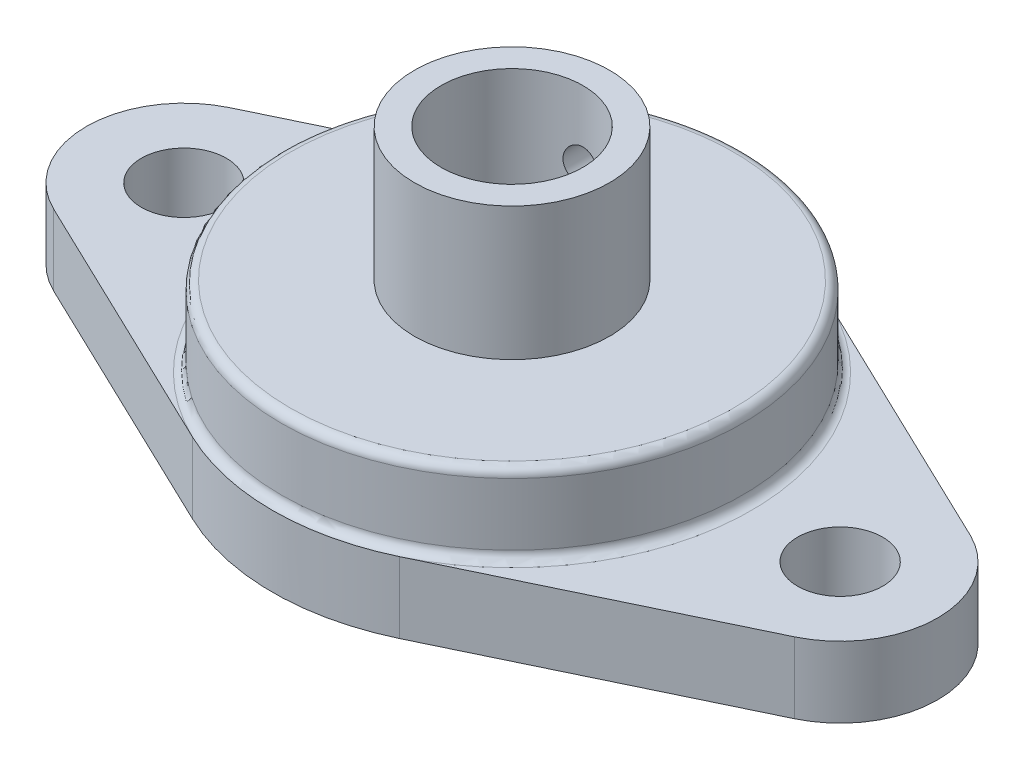
SolidWorks part; units mm, degrees
other "细节项目1"
ref_plane "前视" through (0, 0, 0) normal (0, 0, 1) x (1, 0, 0)
ref_plane "上视" through (0, 0, 0) normal (0, 1, 0) x (1, 0, 0)
ref_plane "右视" through (0, 0, 0) normal (1, 0, 0) x (0, 0, -1)
sketch "草图1" plane through (0, 0, 0) normal (0, 1, 0) x (1, 0, 0)
  line L0 (-20.8784, 4.9592) -> (-5.8378, 12.1725)
  line L1 (-20.8784, -4.9592) -> (-5.8378, -12.1725)
  line L2 (5.8378, -12.1725) -> (20.8784, -4.9592)
  line L3 (5.8378, 12.1725) -> (20.8784, 4.9592)
  circle A0 centre (0, 0) radius 13.5
  circle A1 centre (-18.5, 0) radius 2.4
  circle A2 centre (18.5, 0) radius 2.4
  arc A3 (-20.8784, 4.9592) -> (-20.8784, -4.9592) centre (-18.5, 0) ccw
  arc A4 (20.8784, -4.9592) -> (20.8784, 4.9592) centre (18.5, 0) ccw
  dimension "D1" = 27
  dimension "D4" = 4.8
  dimension "D5" = 4.8
  dimension "D6" = 11
  dimension "D7" = 11
  dimension "D2" = 37
  dimension "D3" = 18.5
extrude "凸台-拉伸1" add sketch "草图1" along normal blind 4 contours A3 L1 A0 L0 | A3 A1 | A0 | A4 L3 A0 L2 | A4 A2 region at (-13.2268, 0, -8.292) region at (0, 0, 0) region at (13.2268, 0, -8.292)
sketch "草图2" plane through (0, 4, 0) normal (0, 1, 0) x (1, 0, 0)
  circle A0 centre (0, 0) radius 13
  dimension "D1" = 26
extrude "凸台-拉伸2" add sketch "草图2" along normal blind 4.5
sketch "草图3" plane through (0, 8.5, 0) normal (0, 1, 0) x (1, 0, 0)
  circle A0 centre (0, 0) radius 5.5
  dimension "D1" = 11
extrude "凸台-拉伸3" add sketch "草图3" along normal blind 7.5
sketch "草图4" plane through (0, 16, 0) normal (0, 1, 0) x (1, 0, 0)
  circle A0 centre (0, 0) radius 4
  dimension "D1" = 8
extrude "切除-拉伸1" cut sketch "草图4" against normal up to next
fillet "圆角1" radius 0.5 2 edges at (0, 8.5, 13) (0, 4, 13)
sketch "草图6" plane through (0, 0, 0) normal (0, 0, 1) x (1, 0, 0)
  circle A0 centre (0, 12) radius 1
  dimension "D2" = 2
  dimension "D1" = 12
extrude "切除-拉伸2" cut sketch "草图6" against normal up to next
